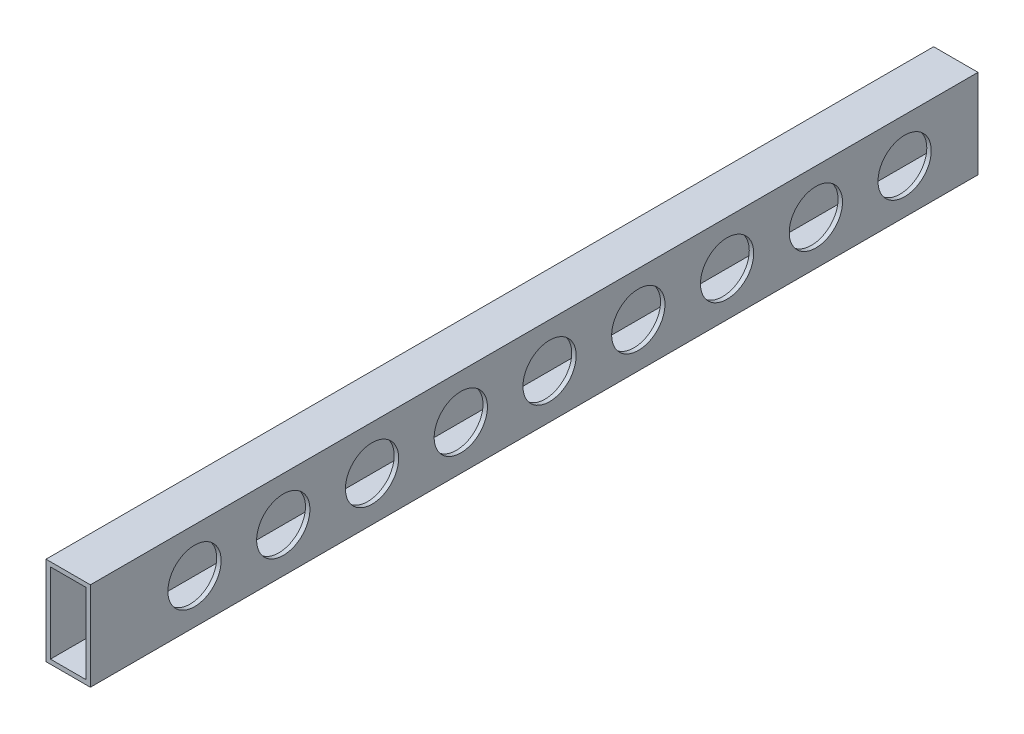
SolidWorks part; units mm, degrees
ref_plane "Front Plane" through (0, 0, 0) normal (0, 0, 1) x (1, 0, 0)
ref_plane "Top Plane" through (0, 0, 0) normal (0, 1, 0) x (1, 0, 0)
ref_plane "Right Plane" through (0, 0, 0) normal (1, 0, 0) x (0, 0, -1)
sketch "Sketch1" plane through (0, 0, 0) normal (0, 0, 1) x (1, 0, 0)
  line L1 (-15.875, -31.75) -> (15.875, -31.75)
  line L2 (-15.875, -31.75) -> (-15.875, 31.75)
  line L3 (-15.875, 31.75) -> (15.875, 31.75)
  line L4 (15.875, -31.75) -> (15.875, 31.75)
  line L5 (-15.875, -31.75) -> (15.875, 31.75) construction
  line L6 (-15.875, 31.75) -> (15.875, -31.75) construction
  line L7 (-12.7, -28.575) -> (12.7, -28.575)
  line L8 (-12.7, -28.575) -> (-12.7, 28.575)
  line L9 (-12.7, 28.575) -> (12.7, 28.575)
  line L10 (12.7, -28.575) -> (12.7, 28.575)
  line L11 (-12.7, -28.575) -> (12.7, 28.575) construction
  line L12 (-12.7, 28.575) -> (12.7, -28.575) construction
  point P0 (0, 0)
  point P1 (0, 0)
  point P7 (0, 0)
  dimension "D1" = 31.75
  dimension "D2" = 63.5
  dimension "D3" = 3.175
  dimension "D4" = 3.175
extrude "Boss-Extrude1" add sketch "Sketch1" along normal blind 635
sketch "Sketch2" plane through (15.875, 0, 0) normal (1, 0, 0) x (0, 0, -1)
  line L1 (-635, -31.75) -> (-635, 31.75) construction
  circle A0 centre (-560.5018, 0) radius 19.05
  circle A1 centre (-497.0018, 0) radius 19.05
  circle A2 centre (-433.5018, 0) radius 19.05
  circle A3 centre (-370.0018, 0) radius 19.05
  circle A4 centre (-306.5018, 0) radius 19.05
  circle A5 centre (-243.0018, 0) radius 19.05
  circle A6 centre (-179.5018, 0) radius 19.05
  circle A7 centre (-116.0018, 0) radius 19.05
  circle A8 centre (-52.5018, 0) radius 19.05
  dimension "D1" = 38.1
  dimension "D2" = 74.4982
  dimension "D3" = 9
extrude "Cut-Extrude1" cut sketch "Sketch2" against normal up to surface (31.75 mm away) up to face at (-15.875, 0, 317.5)
